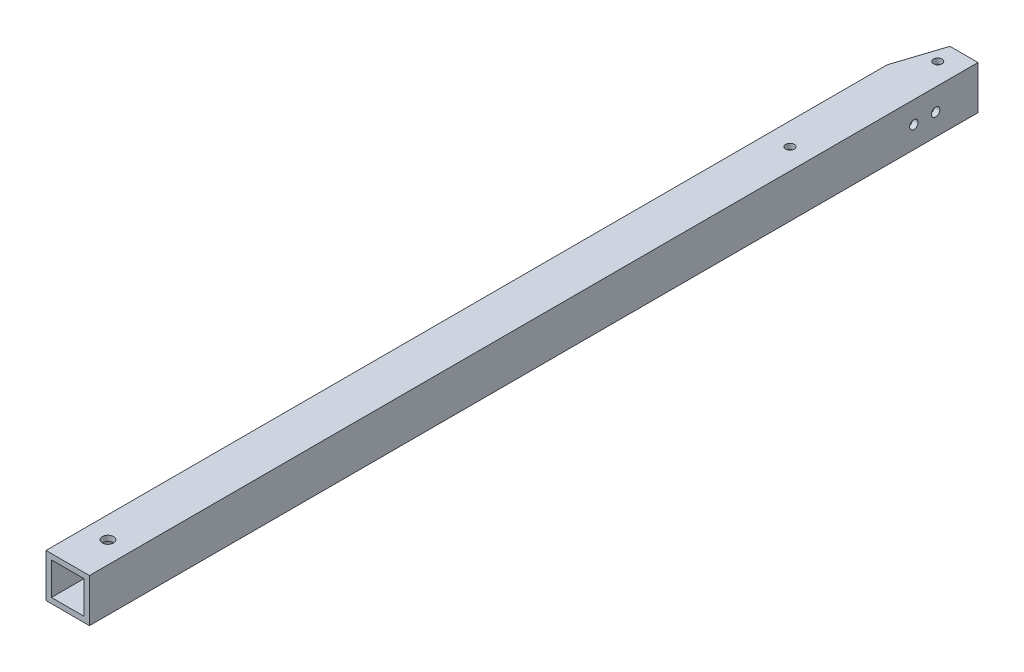
SolidWorks part; units mm, degrees
ref_plane "Front Plane" through (0, 0, 0) normal (0, 0, 1) x (1, 0, 0)
ref_plane "Top Plane" through (0, 0, 0) normal (0, 1, 0) x (1, 0, 0)
ref_plane "Right Plane" through (0, 0, 0) normal (1, 0, 0) x (0, 0, -1)
sketch "Sketch1" plane through (0, 0, 0) normal (0, 0, 1) x (1, 0, 0)
  line L0 (-9.525, 9.525) -> (9.525, 9.525)
  line L2 (-12.7, 12.7) -> (12.7, 12.7)
  line L3 (-12.7, 12.7) -> (-12.7, -12.7)
  line L4 (-12.7, -12.7) -> (12.7, -12.7)
  line L5 (12.7, 12.7) -> (12.7, -12.7)
  line L10 (9.525, 9.525) -> (9.525, -9.525)
  line L11 (-9.525, -9.525) -> (9.525, -9.525)
  line L12 (-9.525, 9.525) -> (-9.525, -9.525)
  point P12 (0, 12.7)
  point P14 (12.7, 0)
  dimension "Wall Thickness" = 3.175
  dimension "Outside Width" = 25.4
  dimension "Outside Height" = 25.4
  dimension "Inside Height" = 19.05
  dimension "Inside Width" = 19.05
sketch "Sketch2" plane through (0, 0, 0) normal (1, 0, 0) x (0, 0, -1)
  line L0 (266.7, 0) -> (-266.7, 0)
  point P4 (0, 0)
  point P7 (-266.7, 0)
  point P10 (266.7, 0)
  dimension "Length" = 533.4
sketch "Sketch3" plane through (0, 0, 0) normal (0, 0, 1) x (1, 0, 0)
  line L21 (12.7, 12.7) -> (-12.7, 12.7)
  line L22 (12.7, -12.7) -> (12.7, 12.7)
  line L23 (-12.7, -12.7) -> (12.7, -12.7)
  line L24 (-12.7, 12.7) -> (-12.7, -12.7)
  line L25 (12.7, 12.7) -> (-12.7, 12.7)
  line L26 (12.7, -12.7) -> (12.7, 12.7)
  line L27 (-12.7, -12.7) -> (12.7, -12.7)
  line L28 (-12.7, 12.7) -> (-12.7, -12.7)
  line L29 (9.525, 9.525) -> (-9.525, 9.525)
  line L30 (9.525, -9.525) -> (9.525, 9.525)
  line L31 (-9.525, -9.525) -> (9.525, -9.525)
  line L32 (-9.525, 9.525) -> (-9.525, -9.525)
  line L33 (9.525, 9.525) -> (-9.525, 9.525)
  line L34 (9.525, -9.525) -> (9.525, 9.525)
  line L35 (-9.525, -9.525) -> (9.525, -9.525)
  line L36 (-9.525, 9.525) -> (-9.525, -9.525)
  dimension "D1" = 0
  dimension "D2" = 0
extrude "Boss-Extrude1" add sketch "Sketch3" along normal up to vertex (266.7 mm away) and the other way up to vertex (266.7 mm away) up to point (0, 0, 266.7) other way up to point (0, 0, -266.7)
sketch "Drawing Reference" plane through (0, 0, 0) normal (1, 0, 0) x (0, 0, -1)
  line L0 (-266.7, 0) -> (266.7, 0) construction
  line L1 (0, -12.7) -> (0, 12.7) construction
  line L2 (-266.7, -12.7) -> (266.7, -12.7) construction
  line L5 (-266.7, 12.7) -> (266.7, 12.7) construction
  point P7 (-248.412, 0)
  point P8 (248.412, 0)
  dimension "D1" = 18.288
sketch "Sketch4" plane through (0, 12.7, 0) normal (0, 1, 0) x (1, 0, 0)
  line L7 (-12.7, 225.0135) -> (-12.7, 266.7)
  line L8 (-188.5374, -316.1583) -> (5.0007, 279.4906) construction
  line L10 (-12.7, -266.7) -> (-12.7, 266.7) construction
  line L11 (-12.7, 266.7) -> (12.7, 266.7)
  line L12 (12.7, 266.7) -> (12.7, 252.73)
  line L13 (12.7, -266.7) -> (12.7, 266.7) construction
  line L14 (12.7, 252.73) -> (-3.6943, 252.73)
  line L15 (-3.6943, 252.73) -> (-12.7, 225.0135)
  dimension "D1" = 13.97
extrude "Cut-Extrude1" cut sketch "Sketch4" against normal blind 25.4
sketch "Sketch5" plane through (0, -12.7, 0) normal (0, -1, 0) x (1, 0, 0)
  circle A0 centre (-0.2763, -181.0535) radius 9.525
extrude "Cut-Extrude2" cut sketch "Sketch5" against normal blind 3.175
sketch "Sketch6" plane through (12.7, 0, 0) normal (1, 0, 0) x (0, 0, -1)
  line L0 (252.73, 0) -> (215.265, 0) construction
  line L1 (252.73, -12.7) -> (252.73, 12.7) construction
  line L2 (215.265, 0) -> (227.965, 0) construction
  dimension "D1" = 37.465
hole_wizard "#10 Clearance Hole2" positions "Sketch9" profile "Sketch10" hole size "#10" standard "ANSI Inch" end condition through all
sketch "Sketch9" plane through (0, 12.7, 0) normal (0, 1, 0) x (1, 0, 0)
  point P0 (0.3823, 155.1367)
  point P3 (0.3823, 241.5232)
sketch "Sketch10" plane through (0.3823, 12.7, -155.1367) normal (1, 0, 0) x (0, 0, 1)
  line L0 (0, 0) -> (0, 25.4)
  line L1 (0, 25.4) -> (2.4892, 25.4)
  line L2 (2.4892, 25.4) -> (2.4892, 0)
  line L5 (2.4892, 0) -> (0, 0)
  line L11 (0, -6.35) -> (0, 107.95) construction
  dimension "Thru Hole Dia." = 4.9784
  dimension "Thru Hole Depth" = 25.4
hole_wizard "1/4 Clearance Hole2" positions "Sketch13" profile "Sketch14" hole size "1/4" standard "ANSI Inch" end condition through all
sketch "Sketch13" plane through (0, 12.7, 0) normal (0, 1, 0) x (1, 0, 0)
  point P0 (0, -243.2081)
sketch "Sketch14" plane through (0, 12.7, 243.2081) normal (1, 0, 0) x (0, 0, 1)
  line L0 (0, 0) -> (0, 25.4)
  line L1 (0, 25.4) -> (3.2639, 25.4)
  line L2 (3.2639, 25.4) -> (3.2639, 0)
  line L5 (3.2639, 0) -> (0, 0)
  line L11 (0, -6.35) -> (0, 107.95) construction
  dimension "Thru Hole Dia." = 6.5278
  dimension "Thru Hole Depth" = 25.4
hole_wizard "#10 Clearance Hole3" positions "Sketch15" profile "Sketch16" hole size "#10" standard "ANSI Inch"
sketch "Sketch15" plane through (12.7, 0, 0) normal (1, 0, 0) x (0, 0, -1)
  point P0 (227.965, 0)
  point P4 (215.265, 0)
sketch "Sketch16" plane through (12.7, 0, -227.965) normal (0, 1, 0) x (0, 0, -1)
  line L0 (0, 0) -> (0, 6.5757)
  line L1 (0, 6.5757) -> (2.4892, 5.08)
  line L2 (2.4892, 5.08) -> (2.4892, 0)
  line L5 (2.4892, 0) -> (0, 0)
  line L10 (0, 6.5757) -> (-2.4892, 5.08) construction
  line L11 (0, -6.35) -> (0, 107.95) construction
  dimension "Hole Dia." = 4.9784
  dimension "Hole Depth" = 5.08
  dimension "Drill Angle" = 118
equation "\"D1@Drawing Reference\"=\"Outside Width@Sketch1\" * 0.72"
